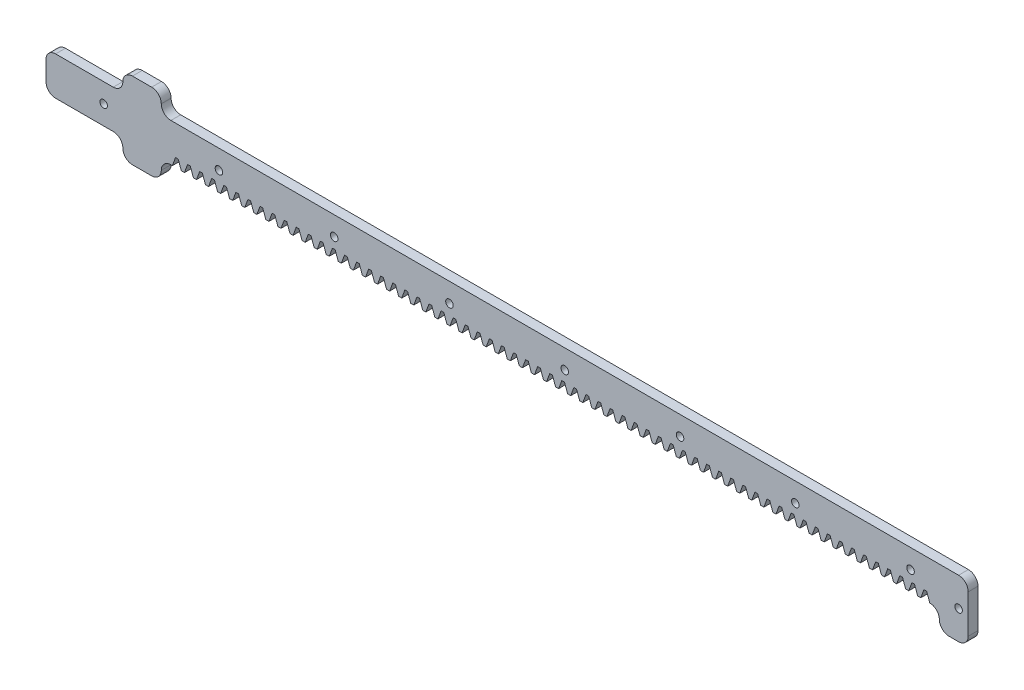
SolidWorks part; units mm, degrees
material "PC High Viscosity"
ref_plane "Front Plane" through (0, 0, 0) normal (0, 0, 1) x (1, 0, 0)
ref_plane "Top Plane" through (0, 0, 0) normal (0, 1, 0) x (1, 0, 0)
ref_plane "Right Plane" through (0, 0, 0) normal (1, 0, 0) x (0, 0, -1)
sketch "Sketch1" plane through (0, 0, 0) normal (0, 0, 1) x (1, 0, 0)
  line L0 (50.8, 0) -> (50.8, -12.7)
  line L1 (0, 0) -> (590.55, 0)
  line L2 (0, 0) -> (0, 25.4)
  line L3 (0, 25.4) -> (609.6, 25.4)
  line L4 (609.6, 0) -> (609.6, 25.4)
  line L5 (50.8, 38.1) -> (76.2, 38.1)
  line L6 (76.2, 38.1) -> (76.2, 25.4)
  line L7 (50.8, 38.1) -> (50.8, 25.4)
  line L8 (76.2, 0) -> (76.2, -12.7)
  line L9 (76.2, -12.7) -> (50.8, -12.7)
  line L10 (590.55, 0) -> (590.55, -12.7)
  line L11 (609.6, 10.0162) -> (603.25, 13.6823) construction
  line L12 (603.25, 13.6823) -> (596.9, 10.0162) construction
  line L13 (596.9, 10.0162) -> (596.9, 2.6838) construction
  line L14 (596.9, 2.6838) -> (603.25, -0.9823) construction
  line L15 (603.25, -0.9823) -> (609.6, 2.6838) construction
  line L16 (609.6, 2.6838) -> (609.6, 10.0162) construction
  line L17 (609.6, 0) -> (609.6, -12.7)
  line L18 (609.6, -12.7) -> (590.55, -12.7)
  circle A0 centre (603.25, 6.35) radius 2.4892
  circle A1 centre (603.25, 6.35) radius 6.35 construction
  dimension "D5" = 4.9784
  dimension "D6" = 12.7
  dimension "D7" = 12.7
  dimension "D1" = 609.6
  dimension "D2" = 25.4
  dimension "D3" = 25.4
  dimension "D4" = 50.8
  dimension "D8" = 19.05
  dimension "D9" = 12.7
extrude "Boss-Extrude1" add sketch "Sketch1" along normal blind 6.477 contours L6 L5 L3 | L1 L4 L3 L2 A0 | L9 L8 L1 region at (63.5, -6.35, 0) region at (308.9784, 12.4144, 0) region at (63.5, 31.75, 0)
fillet "Fillet2" radius 6.35 14 edges at (76.2, 38.1, 3.2385) (76.2, 25.4, 3.2385) (609.6, 25.4, 3.2385) (76.2, 0, 3.2385) (76.2, -12.7, 3.2385) (50.8, -12.7, 3.2385) (50.8, 0, 3.2385) (0, 0, 3.2385) (50.8, 38.1, 3.2385) (50.8, 25.4, 3.2385) (0, 25.4, 3.2385) (590.55, 0, 3.2385) (590.55, -12.7, 3.2385) (609.6, -12.7, 3.2385)
sketch "Sketch2" plane through (0, 0, 6.477) normal (0, 0, 1) x (1, 0, 0)
  line L0 (584.2, 0) -> (82.55, 0)
  line L1 (82.55, 0) -> (82.55, 5.715)
  line L2 (82.55, 5.715) -> (584.2, 5.715)
  line L3 (584.2, 5.715) -> (584.2, 0)
  line L5 (583.2755, 2.54) -> (575.111, 2.54) construction
  line L6 (584.2, 0) -> (582.1199, 5.715)
  line L7 (82.55, 0) -> (584.2, 0) construction
  line L8 (578.2688, 0) -> (584.2, 0)
  line L9 (579.389, 0) -> (584.2, 0)
  line L10 (582.1199, 5.715) -> (580.3488, 5.715)
  line L11 (584.2, 0) -> (578.2688, 0)
  line L12 (578.2688, 0) -> (580.3488, 5.715)
  line L13 (580.3488, 5.715) -> (582.1199, 5.715)
  line L14 (584.2, 0) -> (578.2688, 0)
  line L15 (580.3488, 5.715) -> (582.1199, 5.715)
  line L16 (584.2, 0) -> (578.2688, 0)
  line L17 (578.2688, 0) -> (576.0355, 0)
  line L19 (582.1199, 5.715) -> (580.3488, 5.715) construction
  line L20 (578.2688, 0) -> (576.0355, 0) construction
  point P8 (579.1932, 2.54)
  point P16 (583.2755, 2.54)
  point P17 (575.111, 2.54)
  dimension "D1" = 70
  dimension "D2" = 2.54
  dimension "D3" = 3.175
  dimension "D4" = 70
  dimension "D5" = 1.7711
extrude "Cut-Extrude1" cut sketch "Sketch2" against normal through all contours L12 L0 L8 L6 L2 region at (581.2344, 2.343, 6.477)
pattern_linear "LPattern1" count 63 spacing 7.9796 along (-1, 0, 0) of "Cut-Extrude1"
sketch "Sketch3" plane through (0, 0, 6.477) normal (0, 0, 1) x (1, 0, 0)
  line L0 (82.55, 25.4) -> (603.25, 25.4) construction
  line L1 (609.6, 19.05) -> (609.6, -6.35) construction
  circle A0 centre (571.5, 12.7) radius 2.4892
  dimension "D2" = 4.9784
  dimension "D4" = 12.7
  dimension "D5" = 38.1
extrude "Cut-Extrude2" cut sketch "Sketch3" against normal through all
pattern_linear "LPattern2" count 8 spacing 76.2 along (-1, 0, 0) of "Cut-Extrude2"
